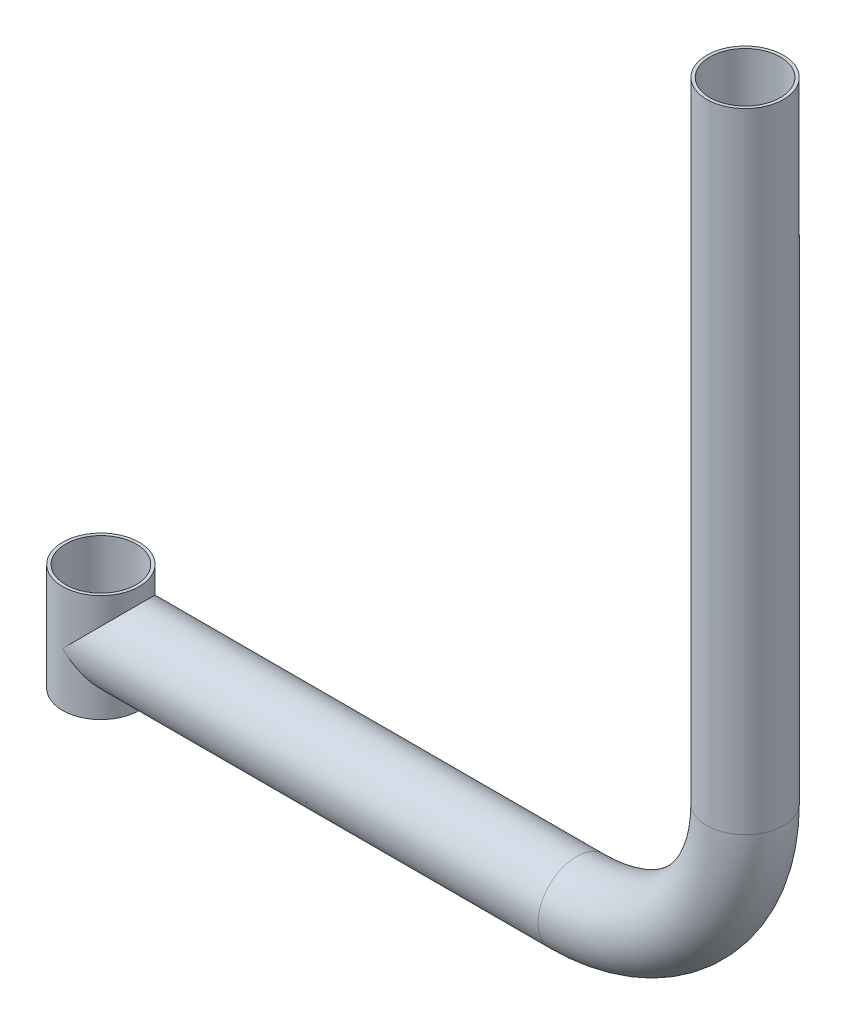
SolidWorks part; units mm, degrees
ref_plane "前基準面" through (0, 0, 0) normal (0, 0, 1) x (1, 0, 0)
ref_plane "上基準面" through (0, 0, 0) normal (0, 1, 0) x (1, 0, 0)
ref_plane "右基準面" through (0, 0, 0) normal (1, 0, 0) x (0, 0, -1)
sketch "草圖1" plane through (0, 0, 0) normal (0, 1, 0) x (1, 0, 0)
  circle A0 centre (0, 0) radius 12.5
  circle A1 centre (0, 0) radius 11.5
  dimension "D1" = 25
  dimension "D2" = 23
extrude "填料-伸長1" add sketch "草圖1" along normal mid plane 35
sketch "草圖2" plane through (0, 0, 0) normal (1, 0, 0) x (0, 0, -1)
  circle A0 centre (0, 0) radius 12.5
  circle A1 centre (0, 0) radius 11.5
  dimension "D1" = 25
  dimension "D2" = 23
sketch "草圖6" plane through (0, 0, 0) normal (0, 0, 1) x (1, 0, 0)
  line L0 (0, 0) -> (155, 0)
  line L1 (210, 55) -> (210, 260)
  arc A0 (155, 0) -> (210, 55) centre (155, 55) ccw
  point P6 (210, 0)
  dimension "D3" = 55
  dimension "D1" = 210
  dimension "D2" = 260
sweep "掃出1" add profiles "草圖2" path "草圖6"
extrude "除料-伸長2" cut sketch "草圖1<3>" against normal mid plane 800 contours A1
sketch "草圖1<3>" plane through (0, 0, 0) normal (0, 1, 0) x (1, 0, 0) same geometry as "草圖1"
